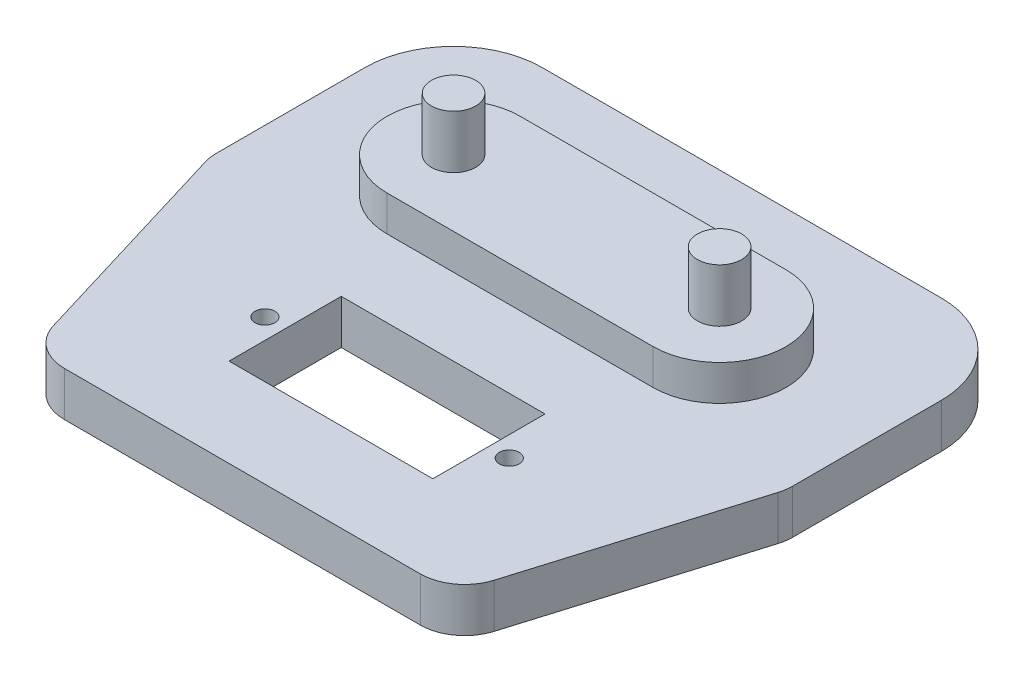
SolidWorks part; units mm, degrees
ref_plane "Front Plane" through (0, 0, 0) normal (0, 0, 1) x (1, 0, 0)
ref_plane "Top Plane" through (0, 0, 0) normal (0, 1, 0) x (1, 0, 0)
ref_plane "Right Plane" through (0, 0, 0) normal (1, 0, 0) x (0, 0, -1)
sketch "Sketch1" plane through (0, 0, 0) normal (0, 1, 0) x (1, 0, 0)
  line L0 (0, 28.1625) -> (0, -28.1625) construction
  line L2 (-32.5, 1.4022) -> (-32.5, 18.1625)
  line L3 (-22.5, 28.1625) -> (22.5, 28.1625)
  line L5 (11.49, -5.5125) -> (0, -11.8375) construction
  line L6 (-32.5, 28.1625) -> (0, 0) construction
  line L7 (-11.49, -18.1625) -> (11.49, -18.1625)
  line L8 (-11.49, -18.1625) -> (-11.49, -5.5125)
  line L9 (-11.49, -5.5125) -> (11.49, -5.5125)
  line L11 (-11.49, -18.1625) -> (0, -11.8375) construction
  line L12 (-11.49, -5.5125) -> (0, -11.8375) construction
  line L17 (15, 18.1625) -> (-15, 18.1625)
  line L18 (-15, 3.1625) -> (15, 3.1625)
  line L19 (-32.2858, -0.0455) -> (-24.8546, -24.6103)
  line L20 (-20.0688, -28.1625) -> (20.0688, -28.1625)
  line L21 (11.49, -18.1625) -> (0, -11.8375) construction
  line L22 (32.5, 28.1625) -> (0, 0) construction
  line L23 (32.2858, -0.0455) -> (24.8546, -24.6103)
  line L24 (11.49, -18.1625) -> (11.49, -5.5125)
  line L25 (32.5, 1.4022) -> (32.5, 18.1625)
  circle A1 centre (-13.78, -11.8375) radius 1.125
  circle A3 centre (5.085, -11.8375) radius 2.525 construction
  arc A4 (-15, 18.1625) -> (-15, 3.1625) centre (-15, 10.6625) ccw
  circle A5 centre (-15, 10.6625) radius 2.5
  arc A6 (-32.5, 18.1625) -> (-22.5, 28.1625) centre (-22.5, 18.1625) cw
  arc A7 (-24.8546, -24.6103) -> (-20.0688, -28.1625) centre (-20.0688, -23.1625) ccw
  arc A8 (-32.2858, -0.0455) -> (-32.5, 1.4022) centre (-27.5, 1.4022) cw
  arc A9 (32.2858, -0.0455) -> (32.5, 1.4022) centre (27.5, 1.4022) ccw
  arc A10 (24.8546, -24.6103) -> (20.0688, -28.1625) centre (20.0688, -23.1625) cw
  arc A11 (32.5, 18.1625) -> (22.5, 28.1625) centre (22.5, 18.1625) ccw
  circle A12 centre (15, 10.6625) radius 2.5
  arc A13 (15, 18.1625) -> (15, 3.1625) centre (15, 10.6625) cw
  circle A14 centre (13.78, -11.8375) radius 1.125
  point P0 (0, 0)
  point P1 (32.5, 0.6625)
  point P6 (0, -11.8375)
  point P7 (0, -18.1625)
  point P10 (0, 0)
  point P11 (0, 0)
  point P16 (0, 0)
  point P17 (0, -5.5125)
  point P24 (0, 18.1625)
  point P27 (-25.0886, -23.8368)
  point P30 (0, 0)
  point P34 (-23.78, -28.1625)
  point P37 (-32.5, 0.6625)
  point P56 (0, 3.1625)
  point P57 (23.78, -28.1625)
  dimension "D7" = 2.25
  dimension "D10" = 5.05
  dimension "D6" = 5
  dimension "D8" = 5
  dimension "D19" = 10
  dimension "D20" = 5
  dimension "D2" = 32.5
  dimension "D3" = 10
  dimension "D4" = 11.49
  dimension "D5" = 10
  dimension "D9" = 2.29
  dimension "D11" = 56.325
  dimension "D12" = 15
  dimension "D13" = 22.5
  dimension "D14" = 10
  dimension "D15" = 10
  dimension "D16" = 28.1625
  dimension "D17" = 12.65
  dimension "D18" = 5.085
extrude "Boss-Extrude1" add sketch "Sketch1" along normal blind 5 contours L25 A11 L3 A6 L2 A8 L19 A7 L20 A10 L23 A9 L17 A13 L18 A4 A1 L24 L7 L8 L9 A14 region at (0, 0, -0.224)
extrude "Boss-Extrude2" add sketch "Sketch1<3>" along normal blind 9 contours A13 L17 A4 L18 A5 A12 region at (0, 0, -10.6625)
sketch "Sketch1<3>" plane through (0, 0, 0) normal (0, 1, 0) x (1, 0, 0) same geometry as "Sketch1"
extrude "Boss-Extrude3" add sketch "Sketch1<4>" along normal blind 15 contours A12 | A5 region at (-15, 0, -10.6625) region at (15, 0, -10.6625)
sketch "Sketch1<4>" plane through (0, 0, 0) normal (0, 1, 0) x (1, 0, 0) same geometry as "Sketch1"
